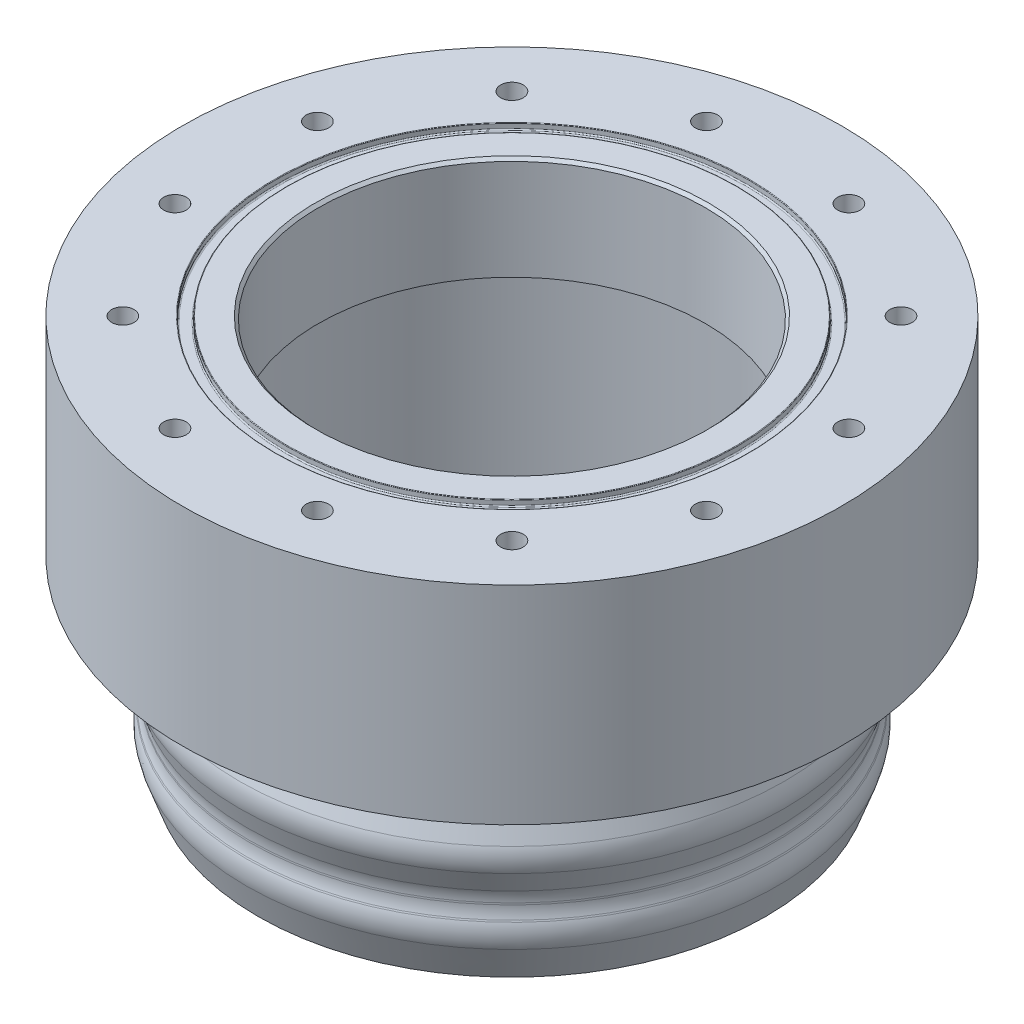
SolidWorks part; units mm, degrees
note: '?' marks a value the reader was unsure of.
material "7075-T6 (SN)"
ref_plane "Front Plane" through (0, 0, 0) normal (0, 0, 1) x (1, 0, 0)
ref_plane "Top Plane" through (0, 0, 0) normal (0, 1, 0) x (1, 0, 0)
ref_plane "Right Plane" through (0, 0, 0) normal (1, 0, 0) x (0, 0, -1)
sketch "Flange profile" plane through (0, 0, 0) normal (0, 0, 1) x (1, 0, 0)
  line L0 (0, 0) -> (0, 94.4875) construction
  line L1 (-42.8625, 22.86) -> (-42.8625, 0)
  line L2 (-73.025, 22.86) -> (-52.5653, 22.86)
  line L3 (-42.8625, 0) -> (-55.7276, 0)
  line L4 (-55.7276, 0) -> (-55.7276, -64.2669)
  line L5 (-42.8625, 22.86) -> (-49.7459, 22.86)
  line L6 (-52.4383, 22.733) -> (-52.4383, 21.7932)
  line L7 (-52.1843, 21.5392) -> (-50.1269, 21.5392)
  line L8 (-49.8729, 21.7932) -> (-49.8729, 22.733)
  line L9 (-73.025, 22.86) -> (-73.025, -23.1513)
  line L11 (-73.025, -23.1513) -> (-48.6828, -23.1513) construction
  line L16 (-58.2676, -47.2363) -> (-58.2676, -50.3097)
  line L17 (-73.025, -23.1513) -> (-58.2676, -23.1513)
  line L18 (-48.9204, -44.4628) -> (-48.9204, -68.3701) construction
  line L19 (-58.2676, -47.2363) -> (-61.3156, -38.862)
  line L20 (-61.3156, -38.862) -> (-58.2676, -30.4877)
  line L21 (-58.2676, -30.4877) -> (-58.2676, -23.1513)
  line L22 (-59.7916, -54.4969) -> (-56.2356, -64.2669)
  line L23 (-56.2356, -64.2669) -> (-55.7276, -64.2669)
  line L24 (-58.2676, -50.3097) -> (-59.7916, -54.4969)
  arc A0 (-49.8729, 21.7932) -> (-50.1269, 21.5392) centre (-50.1269, 21.7932) cw
  arc A1 (-52.1843, 21.5392) -> (-52.4383, 21.7932) centre (-52.1843, 21.7932) cw
  arc A2 (-49.7459, 22.86) -> (-49.8729, 22.733) centre (-49.7459, 22.733) ccw
  arc A3 (-52.4383, 22.733) -> (-52.5653, 22.86) centre (-52.5653, 22.733) ccw
  point P27 (-49.8729, 21.5392)
  point P32 (-49.8729, 22.86)
  point P35 (-52.4383, 22.86)
  dimension "D20" = 61.722
  dimension "D22" = 0.508
  dimension "D12" = 0.254
  dimension "D14" = 0.254
  dimension "D18" = 0.127
  dimension "D21" = 0.127
  dimension "D3" = 73.025
  dimension "D4" = 55.7276
  dimension "D5" = 4.064
  dimension "D6" = 52.4383
  dimension "D7" = 2.5654
  dimension "D8" = 1.3208
  dimension "D9" = 2.54
  dimension "D10" = 42.8625
  dimension "D11" = 20
  dimension "D13" = 2.54
  dimension "D15" = 20
  dimension "D16" = 46.0113
  dimension "D17" = 5.588
  dimension "D23" = 20
  dimension "D24" = 20
  dimension "D25" = 3.0734
revolve "Flange" add sketch "Flange profile" angle 360 about L0
ref_axis "center of part" through (0, 0, 0) along (0, -1, 0)?
ref_plane "Igniter Ref Plane" through (-71.0946, 0, 0) normal (1, 0, 0) x (0, 0, -1)
ref_plane "Assembly Bolt Offset Angle" through (0, 0, 0) normal (-0.2588, 0, 0.9659) x (0.9659, 0, 0.2588)
sketch "Assembly Bolt Insert Diameter" plane through (0, 22.86, 0) normal (0, 1, 0) x (1, 0, 0)
  line L0 (-70.4383, 18.8739) -> (70.4383, -18.8739) construction
  circle A0 centre (-58.8828, 15.7776) radius 2.4892
  dimension "D2" = 4.9784
  dimension "D1" = 60.96
extrude "Assembly Bolt Insert Cut" cut sketch "Assembly Bolt Insert Diameter" against normal blind 21.59
pattern_circular "Assembly Bolts" count 12 over 360 about axis through (0, 0, 0) along (0, 1, 0) of "Assembly Bolt Insert Cut"
sketch "Ref Line for Igniter Cut" plane through (0, 0, 0) normal (0, -1, 0) x (1, 0, 0)
  line L0 (-38.1, 0) -> (-38.1, 25.3157)
thread "Thread6" [suppressed] pitch 1.27 start angle 0, offset 0, length 20.32, pitch 1.27, diameter 4.9784
ref_plane "Plane9" through (-18.2668, 22.86, 58.8828) normal (0, 0, 1) x (-1, 0, 0)
sketch "Thread Profile7" plane through (-18.2668, 22.86, 58.8828) normal (0, 0, 1) x (-1, 0, 0)
  line L0 (0, 0) -> (0, 1.27) construction
  line L1 (0, 0) -> (0.6874, 0.3969)
  line L2 (0.6874, 0.3969) -> (0.6874, 0.5556)
  line L3 (0.6874, 0.5556) -> (0, 0.9525)
  line L4 (0.6874, 0.4762) -> (0, 0.4762) construction
  line L11 (0, 0) -> (0, 0.9525)
  point P2 (0, 0)
  dimension "Pitch" = 1.27
  dimension "Profile_Angle" = 60
  dimension "Profile_Land" = 0.1588
  dimension "Profile_Height" = 0.6874
ref_plane "Plane for Igniter Angle" through (-73.025, 0, 0) normal (-1, 0, 0) x (0, 0, 1)
sketch "Location and sizing of Igniter Cut and Boss" plane through (-73.025, 0, 0) normal (-1, 0, 0) x (0, 0, 1)
  line L5 (0, -55) -> (0, 55) construction
  circle A0 centre (0, 0) radius 8.7122
  dimension "D1" = 17.4244
ref_plane "Igniter Boss Plane" through (-81.3816, 0, 0) normal (1, 0, 0) x (0, 0, -1)
ref_plane "Plane for Pt Cut" through (0, 0, 50.8) normal (0, 0, 1) x (1, 0, 0)
sketch "Pt Cut Diameter" plane through (0, 0, 50.8) normal (0, 0, 1) x (1, 0, 0)
  circle A0 centre (0, -9.525) radius 4.2164
  dimension "D1" = 9.525
  dimension "D2" = 8.4328
extrude "Pt Cut" [suppressed] cut sketch "Pt Cut Diameter" along normal through all
ref_plane "Plane for PT Nipple Cut" through (57.912, 0, 0) normal (1, 0, 0) x (0, 0, -1)
ref_plane "Plane2" through (0, 0, 50.8) normal (0, 0, 1) x (1, 0, 0)
sketch "ref line for Interfence check: bolts and igniter port" plane through (0, 22.86, 0) normal (0, 1, 0) x (1, 0, 0)
  line L0 (-58.8828, 18.2668) -> (-58.8828, 13.2884)
  circle A0 centre (-58.8828, 15.7776) radius 2.4892 construction
ref_plane "Interference check: bolts and igniter port" through (-58.8828, 0, 0) normal (-1, 0, 0) x (0, 0, 1)
fillet "Fillet1" radius 7.62 1 edges at (0, -38.862, -61.3156)
fillet "Fillet2" radius 2.54 2 edges at (0, -23.1513, -58.2676) (0, 0, -55.7276)
fillet "Fillet3" radius 7.62 1 edges at (0, -54.4969, -59.7916)
fillet "Fillet7" radius 7.62 3 edges at (0, -50.3097, -58.2676) (0, -47.2363, -58.2676) (0, -30.4877, -58.2676)
pattern_circular "CirPattern4" [suppressed] count 12 over 360
chamfer "Chamfer1" distance 0.635 angle 45 1 edges at (0, 22.86, -42.8625)
